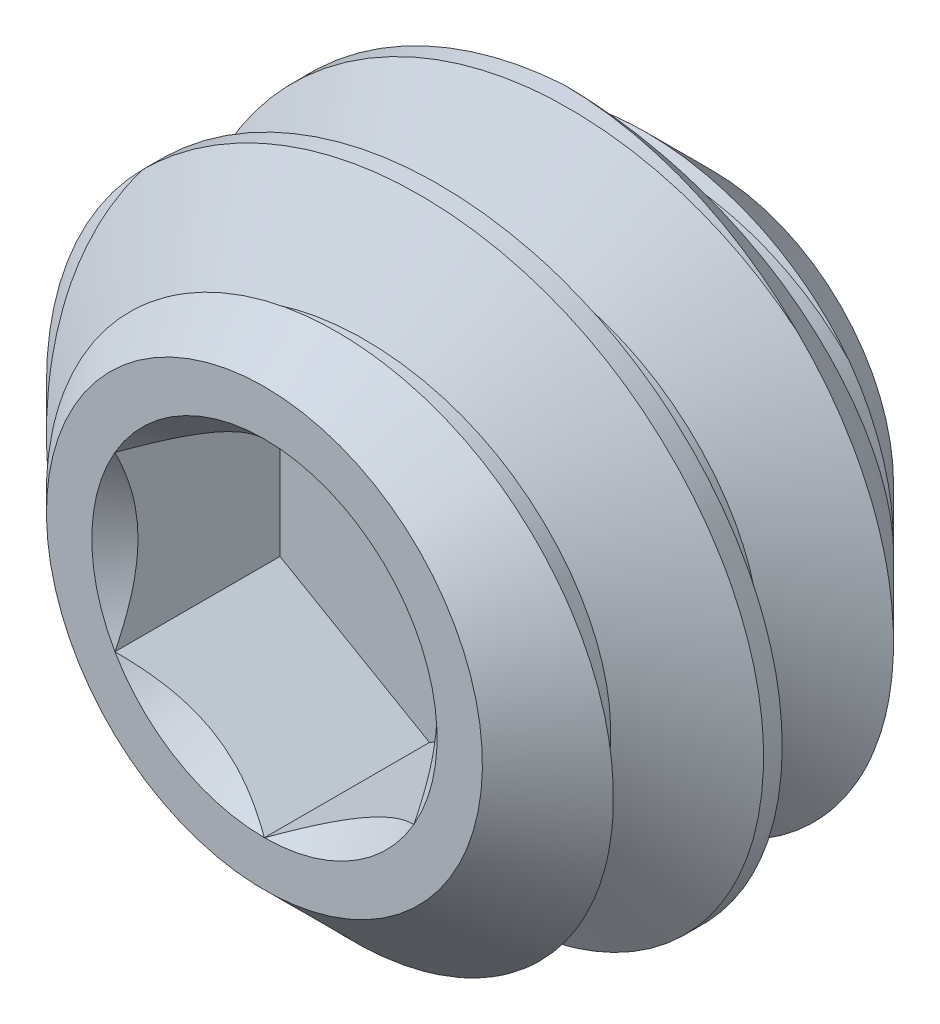
SolidWorks part; units mm, degrees
ref_plane "Front Plane" through (0, 0, 0) normal (0, 0, 1) x (1, 0, 0)
ref_plane "Top Plane" through (0, 0, 0) normal (0, 1, 0) x (1, 0, 0)
ref_plane "Right Plane" through (0, 0, 0) normal (1, 0, 0) x (0, 0, -1)
sketch "Sketch1" plane through (0, 0, 0) normal (1, 0, 0) x (0, 0, -1)
  line L6 (-1.1906, 0) -> (1.1906, 0) construction
  line L7 (-1.1906, 0) -> (-1.1906, 1.7526)
  line L8 (-1.1906, 1.7526) -> (1.1906, 1.7526)
  line L9 (1.1906, 1.7526) -> (1.1906, 0)
  line L10 (1.141, 1.8385) -> (1.5379, 1.1511) construction
  line L15 (1.5379, 1.1511) -> (1.9348, 1.8385) construction
  line L16 (1.9348, 1.8385) -> (1.141, 1.8385) construction
  line L17 (1.1658, 1.7956) -> (1.91, 1.7956)
  line L18 (1.91, 1.7956) -> (1.5875, 1.237)
  line L19 (1.5875, 1.237) -> (1.4883, 1.237)
  line L20 (1.4883, 1.237) -> (1.1658, 1.7956)
  line L21 (1.5379, 1.237) -> (1.5379, 1.1511) construction
  line L22 (1.1906, 1.7526) -> (1.8852, 1.7526) construction
  line L23 (1.5379, 1.8385) -> (1.5379, 1.7526) construction
  line L24 (0.3969, 1.7526) -> (1.1906, 0.9589)
  line L25 (-1.1906, 1.1573) -> (-0.5953, 1.7526)
  line L26 (1.1906, 0.9092) -> (0.6443, 0)
  line L27 (1.1906, -0.9092) -> (0.6443, 0)
  point P4 (0, 0)
  point P23 (1.5379, 1.7956)
  point P29 (-0.3143, 0)
  point P30 (0, 1.7526)
  point P31 (0, -1.7526)
  point P32 (-1.1906, -1.7526)
  dimension "Length" = 2.3813
  dimension "Screw Size Decimal Equivalent" = 3.5052
  dimension "Pitch" = 0.7937
  dimension "D2" = 0.0992
  dimension "D3" = 0.7937
  dimension "D1" = 45
  dimension "D4" = 0.5953
  dimension "D5" = 59
  dimension "D6" = 0.0496
  dimension "D7" = 0.8763
  dimension "D8" = 1.1906
sketch "Sketch10" plane through (0, 0, 0) normal (0, 0, 1) x (1, 0, 0)
  line L1 (0, 0.9165) -> (-0.7938, 0.4583)
  line L2 (-0.7938, 0.4583) -> (-0.7938, -0.4583)
  line L3 (-0.7938, -0.4583) -> (0, -0.9165)
  line L4 (0, -0.9165) -> (0.7937, -0.4583)
  line L5 (0.7937, -0.4583) -> (0.7937, 0.4583)
  line L6 (0.7937, 0.4583) -> (0, 0.9165)
  circle A0 centre (0, 0) radius 0.7938 construction
  dimension "Drive Size" = 1.5875
sketch "Sketch2" plane through (0, 0, 0) normal (1, 0, 0) x (0, 0, -1)
  line L10 (1.1906, 0.9092) -> (0.6443, 0) construction
  line L18 (-1.1906, 1.1573) -> (-0.5953, 1.7526) construction
  line L20 (1.1906, 0.9092) -> (0.6443, 0)
  line L21 (-1.1906, 1.1573) -> (-0.5953, 1.7526)
  line L22 (-0.5953, 1.7526) -> (1.1906, 1.7526)
  line L23 (1.1906, 1.7526) -> (1.1906, 0.9092)
  line L24 (0.6443, 0) -> (-1.1906, 0)
  line L25 (-1.1906, 0) -> (-1.1906, 1.1573)
revolve "Revolve1" add sketch "Sketch2" angle 360 about L24
chamfer "Chamfer1" distance 0.7937 angle 45 1 edges at (0, 1.7526, -1.1906)
sketch "Sketch3" plane through (0, 0, 1.1906) normal (0, 0, 1) x (1, 0, 0)
  line L0 (-0.7938, -0.4583) -> (0, -0.9165) construction
  line L7 (-0.7938, 0.4583) -> (-0.7938, -0.4583) construction
  line L8 (0, 0.9165) -> (-0.7938, 0.4583) construction
  line L9 (0.7937, 0.4583) -> (0, 0.9165) construction
  line L10 (0.7937, -0.4583) -> (0.7937, 0.4583) construction
  line L11 (0, -0.9165) -> (0.7937, -0.4583) construction
  line L12 (-0.7938, -0.4583) -> (0, -0.9165)
  line L13 (-0.7938, 0.4583) -> (-0.7938, -0.4583)
  line L14 (0, 0.9165) -> (-0.7938, 0.4583)
  line L15 (0.7937, 0.4583) -> (0, 0.9165)
  line L16 (0.7937, -0.4583) -> (0.7937, 0.4583)
  line L17 (0, -0.9165) -> (0.7937, -0.4583)
extrude "Cut-Extrude1" cut sketch "Sketch3" against normal up to vertex (0.8763 mm away) up to point (0, 0, 0.3143)
sketch "Sketch4" plane through (0, 0, 1.1906) normal (0, 0, 1) x (1, 0, 0)
  circle A1 centre (0, 0) radius 0.9165
extrude "Cut-Extrude2" cut sketch "Sketch4" against normal up to vertex (0.8763 mm away) draft 45 up to point (0, 0, 0.3143)
ref_axis "Center Axis 1" through (0, 0, -1.7801) along (0, 0, 1)
sketch "Sketch7" plane through (0, 0, -1.1906) normal (0, 0, -1) x (-1, 0, 0)
  circle A3 centre (0, 0) radius 1.7526 construction
  circle A4 centre (0, 0) radius 1.7526
curve "Helix/Spiral1" pitch 0.7937 height 3.1829 radius 1.7526 centre (0, 0, -1.1906) axis (0, 0, 1) start towards (0, 1, 0)
sketch "Sketch8" plane through (0, 0, 0) normal (1, 0, 0) x (0, 0, -1)
  line L0 (1.5875, 1.237) -> (1.4883, 1.237) construction
  line L1 (1.91, 1.7956) -> (1.5875, 1.237) construction
  line L2 (1.1658, 1.7956) -> (1.91, 1.7956) construction
  line L3 (1.4883, 1.237) -> (1.1658, 1.7956) construction
  line L4 (1.5875, 1.237) -> (1.4883, 1.237)
  line L5 (1.91, 1.7956) -> (1.5875, 1.237)
  line L6 (1.1658, 1.7956) -> (1.91, 1.7956)
  line L7 (1.4883, 1.237) -> (1.1658, 1.7956)
sweep "Cut-Sweep1" cut profiles "Sketch8" path "Helix/Spiral1"
equation "\"D3@Helix/Spiral1\"=\"Length@Sketch1\"+(\"Pitch@Sketch1\"*1.01)"
equation "\"D4@Helix/Spiral1\"=\"Pitch@Sketch1\""
equation "\"D2@Sketch1\" = \"Pitch@Sketch1\" / 8"
equation "\"D3@Sketch1\"=\"Pitch@Sketch1\""
equation "\"D4@Sketch1\"=\"Pitch@Sketch1\"*0.75"
equation "\"D6@Sketch1\"=\"D2@Sketch1\"/2"
equation "\"D7@Sketch1\"=0.25*\"Screw Size Decimal Equivalent@Sketch1\""
equation "\"D1@Chamfer1\"=\"D3@Sketch1\""
equation "\"D8@Sketch1\"=\"Pitch@Sketch1\"*1.5"
